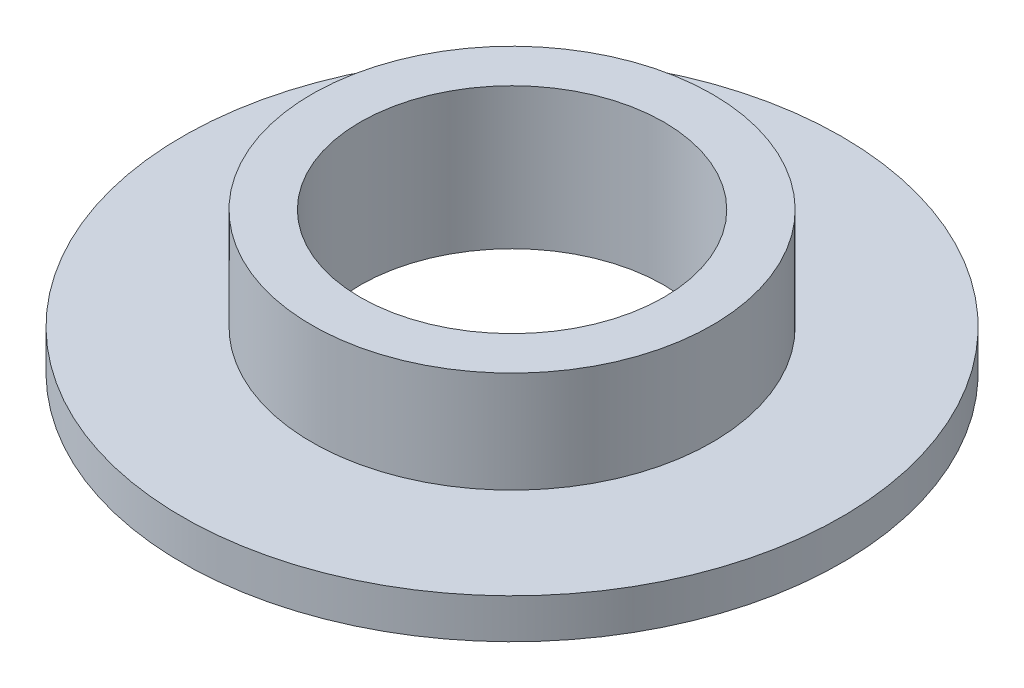
SolidWorks part; units mm, degrees
ref_plane "Front Plane" through (0, 0, 0) normal (0, 0, 1) x (1, 0, 0)
ref_plane "Top Plane" through (0, 0, 0) normal (0, 1, 0) x (1, 0, 0)
ref_plane "Right Plane" through (0, 0, 0) normal (1, 0, 0) x (0, 0, -1)
sketch "Sketch2" plane through (0, 0, 0) normal (1, 0, 0) x (0, 0, -1)
  line L0 (4.1656, 0) -> (9.0424, 0)
  line L1 (9.0424, 0) -> (9.0424, 1.0922)
  line L2 (9.0424, 1.0922) -> (5.4927, 1.0922)
  line L3 (5.4927, 1.0922) -> (5.4927, 3.8735)
  line L4 (5.4927, 3.8735) -> (4.1656, 3.8735)
  line L5 (4.1656, 3.8735) -> (4.1656, 0)
  line L6 (0, -1000) -> (0, 49000) construction
  dimension "D1" = 4.1656
  dimension "D2" = 9.0424
  dimension "D3" = 5.4927
  dimension "D4" = 1.0922
  dimension "D5" = 3.8735
revolve "Revolve1" add sketch "Sketch2" angle 360 about L6
